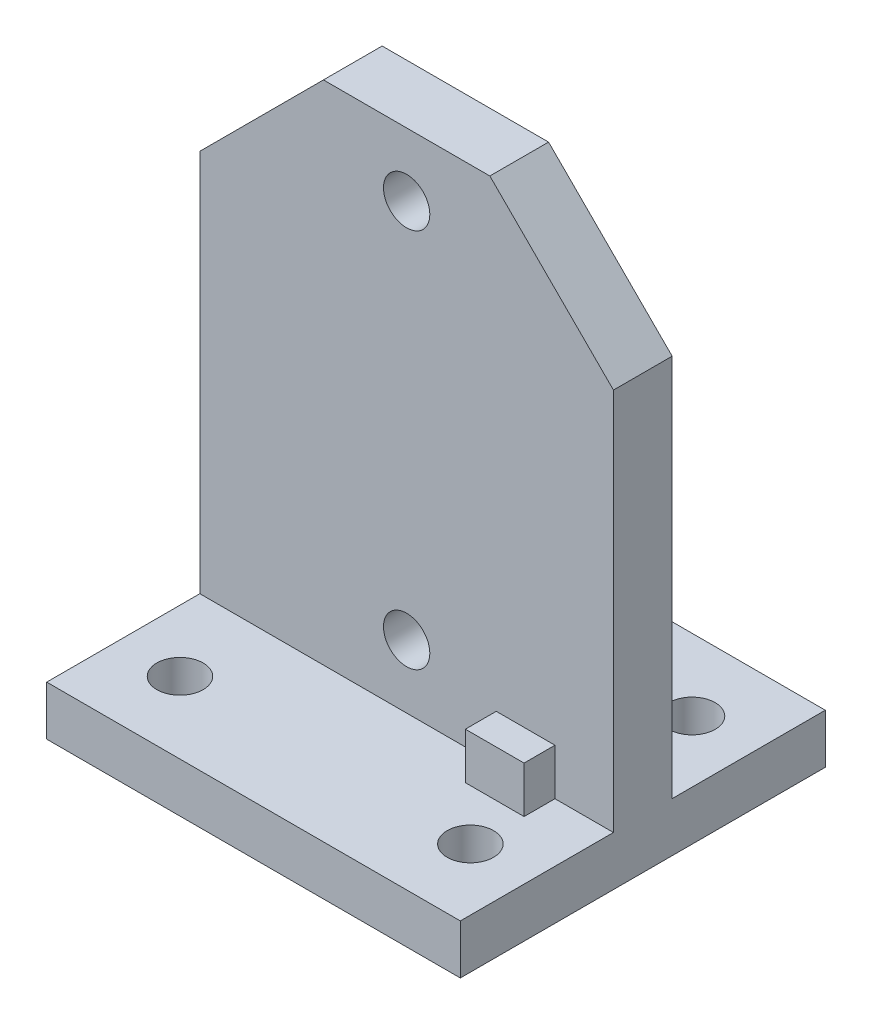
SolidWorks part; units mm, degrees
ref_plane "Front Plane" through (0, 0, 0) normal (0, 0, 1) x (1, 0, 0)
ref_plane "Top Plane" through (0, 0, 0) normal (0, 1, 0) x (1, 0, 0)
ref_plane "Right Plane" through (0, 0, 0) normal (1, 0, 0) x (0, 0, -1)
sketch "Sketch1" plane through (0, 0, 0) normal (0, 0, 1) x (1, 0, 0)
  line L0 (-17, 0) -> (17, 0)
  line L1 (17, 0) -> (17, 31.496)
  line L2 (17, 31.496) -> (6.84, 41.656)
  line L3 (6.84, 41.656) -> (-6.84, 41.656)
  line L4 (17, 31.496) -> (17, 41.656) construction
  line L5 (17, 41.656) -> (6.84, 41.656) construction
  line L6 (0, -55) -> (0, 55) construction
  line L7 (-17, 0) -> (-17, 31.496)
  line L8 (-17, 31.496) -> (-6.84, 41.656)
  line L9 (0, 0) -> (0, 5.207) construction
  circle A0 centre (0, 5.207) radius 1.905
  circle A1 centre (0, 36.449) radius 1.905
  point P4 (0, 0)
  point P11 (0, 0)
  point P13 (0, 41.656)
  dimension "D5" = 3.81
  dimension "D7" = 2
  dimension "D1" = 34
  dimension "D2" = 41.656
  dimension "D3" = 10.16
  dimension "D4" = 10.16
  dimension "D6" = 5.207
  dimension "D8" = 5.207
extrude "Boss-Extrude1" add sketch "Sketch1" along normal mid plane 4.826
sketch "Sketch3" plane through (0, 0, 0) normal (0, 1, 0) x (1, 0, 0)
  line L0 (0, 0) -> (-11.935, 0) construction
  line L1 (-17, -15) -> (17, -15)
  line L2 (-17, -15) -> (-17, 15)
  line L3 (-17, 15) -> (17, 15)
  line L4 (17, -15) -> (17, 15)
  line L5 (-17, -15) -> (17, 15) construction
  line L6 (-17, 15) -> (17, -15) construction
  line L7 (-11.935, 0) -> (-11.935, -9.11) construction
  line L8 (0, 0) -> (0, 8.8012) construction
  circle A0 centre (-11.935, -9.11) radius 1.905
  circle A1 centre (11.935, -9.11) radius 1.905
  circle A2 centre (11.935, 9.11) radius 1.905
  circle A3 centre (-11.935, 9.11) radius 1.905
  point P0 (0, 0)
  dimension "D5" = 3.81
  dimension "D1" = 34
  dimension "D2" = 30
  dimension "D3" = 11.935
  dimension "D4" = 9.11
  dimension "D6" = 2
  dimension "D7" = 2
extrude "Boss-Extrude2" add sketch "Sketch3" against normal blind 4.064
sketch "Sketch4" plane through (0, 0, 0) normal (0, 0, 1) x (1, 0, 0)
  line L0 (7.366, 0) -> (17.2159, 0) construction
  line L2 (-17, 0) -> (17, 0) construction
  line L7 (-17, 0) -> (17, 0) construction
  line L8 (7.366, 0) -> (12.192, 0)
  line L9 (7.366, 0) -> (7.366, 3.81)
  line L10 (7.366, 3.81) -> (12.192, 3.81)
  line L11 (12.192, 0) -> (12.192, 3.81)
  dimension "D1" = 9.8499
  dimension "D2" = 4.826
  dimension "D3" = 3.81
extrude "Boss-Extrude3" add sketch "Sketch4" along normal mid plane 9.906
